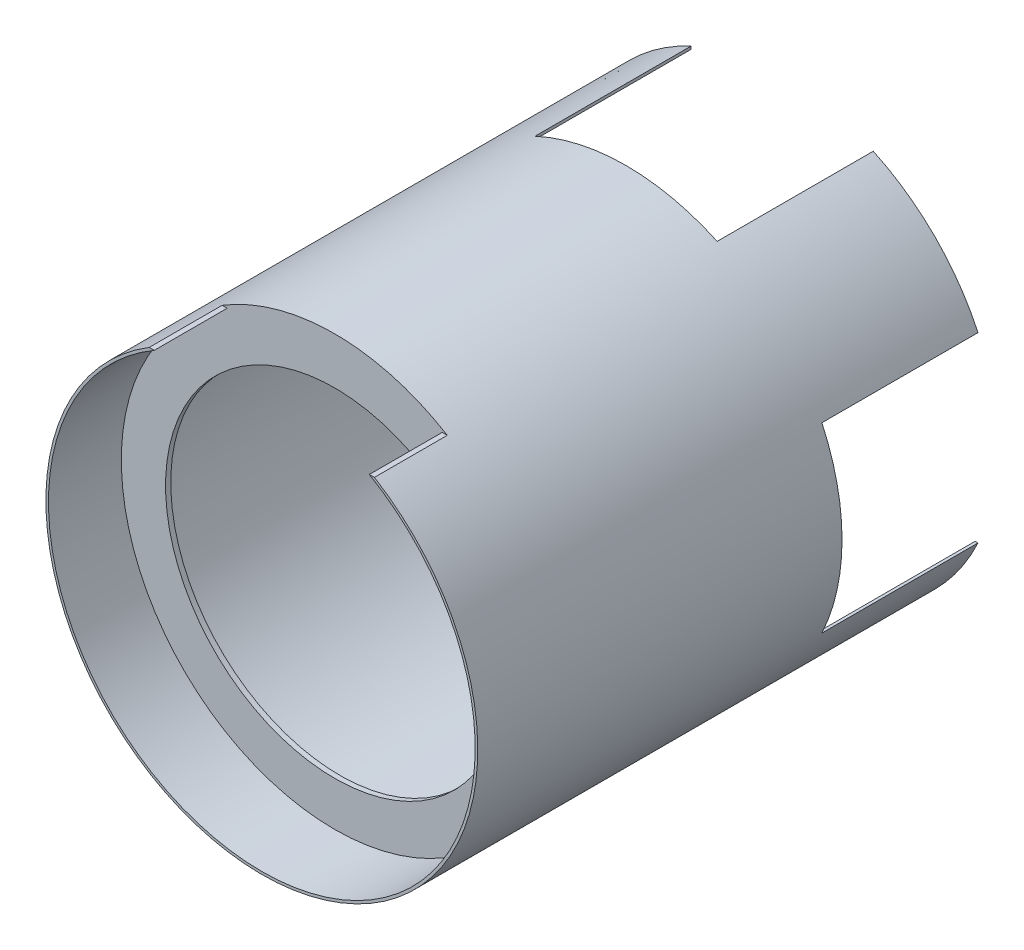
SolidWorks part; units mm, degrees
material "ABS"
ref_plane "前视基准面" through (0, 0, 0) normal (0, 0, 1) x (1, 0, 0)
ref_plane "上视基准面" through (0, 0, 0) normal (0, 1, 0) x (1, 0, 0)
ref_plane "右视基准面" through (0, 0, 0) normal (1, 0, 0) x (0, 0, -1)
sketch "草图1" plane through (0, 0, 0) normal (0, 0, 1) x (1, 0, 0)
  circle A0 centre (0, 0) radius 83
  dimension "D1" = 166
extrude "凸台-拉伸1" add sketch "草图1" along normal blind 100 and the other way blind 100
shell "抽壳1" thickness 1 removed face at (83, 0, -100) removed face at (83, 0, 100)
ref_plane "基准面1" through (0, 0, 70) normal (0, 0, 1) x (1, 0, 0)
sketch "草图2" plane through (0, 0, 70) normal (0, 0, 1) x (1, 0, 0)
  circle A0 centre (0, 0) radius 82.5
  circle A1 centre (0, 0) radius 65
  dimension "D1" = 165
  dimension "D2" = 130
extrude "凸台-拉伸2" add sketch "草图2" along normal blind 2
sketch "草图3" plane through (0, 0, 100) normal (0, 0, 1) x (1, 0, 0)
  line L0 (0, 0) -> (0, 116.4423) construction
  line L1 (43.2734, 70.8267) -> (-43.2734, 70.8267)
  circle A0 centre (0, 0) radius 83 construction
  arc A1 (43.2734, 70.8267) -> (-43.2734, 70.8267) centre (0, 0) ccw
  point P10 (0, 70.8267)
extrude "切除-拉伸1" cut sketch "草图3" against normal up to surface (28 mm away) up to face at (65, 0, 72)
sketch "草图5" plane through (0, 0, 0) normal (0, 1, 0) x (1, 0, 0)
  line L0 (0, 0) -> (0, 70) construction
  line L1 (35, 40) -> (-35, 40)
  line L2 (35, 40) -> (35, 100)
  line L3 (35, 100) -> (-35, 100)
  line L4 (-35, 40) -> (-35, 100)
  line L5 (35, 40) -> (-35, 100) construction
  line L6 (35, 100) -> (-35, 40) construction
  point P0 (0, 70)
  dimension "D1" = 60
  dimension "D2" = 40
  dimension "D3" = 70
extrude "切除-拉伸2" cut sketch "草图5" against normal through all and the other way through all
pattern_circular "阵列(圆周)1" count 4 over 360 about axis through (0, 0, -100) along (0, 0, 1) of "切除-拉伸2"
